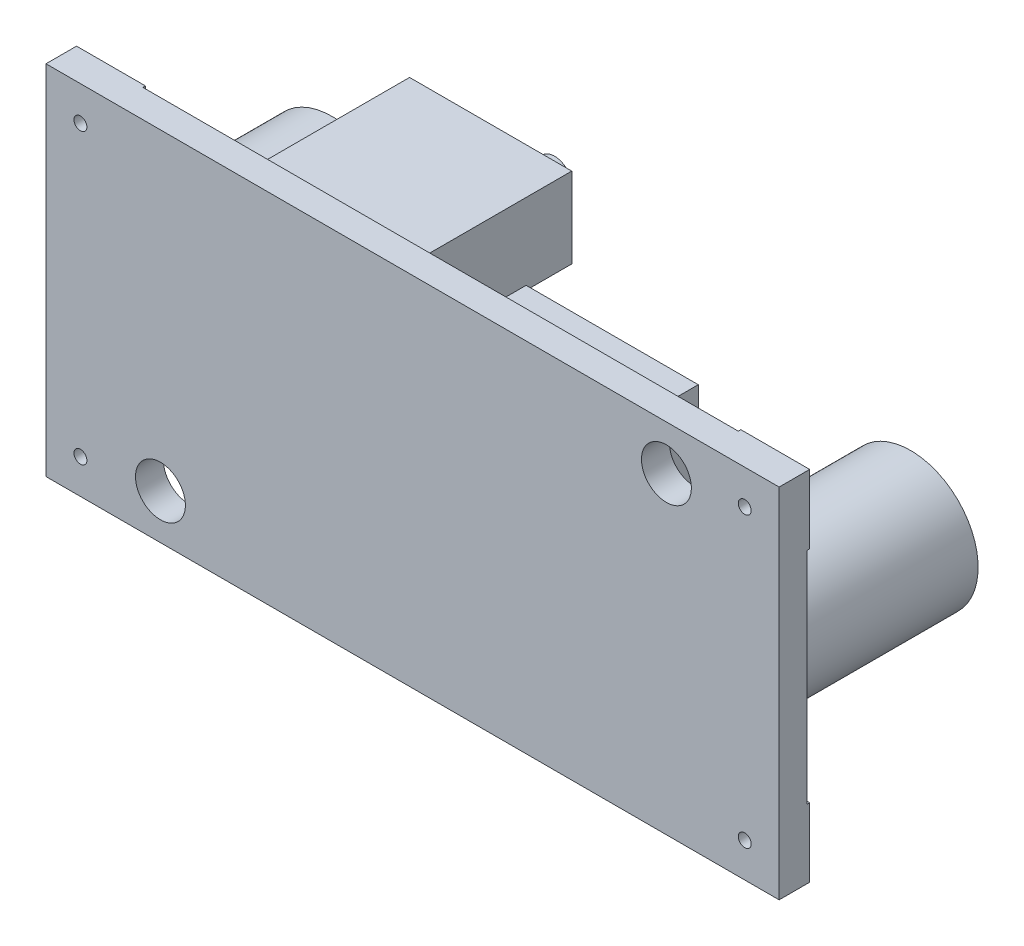
SolidWorks part; units mm, degrees
ref_plane "Front Plane" through (0, 0, 0) normal (0, 0, 1) x (1, 0, 0)
ref_plane "Top Plane" through (0, 0, 0) normal (0, 1, 0) x (1, 0, 0)
ref_plane "Right Plane" through (0, 0, 0) normal (1, 0, 0) x (0, 0, -1)
sketch "Sketch1" plane through (0, 0, 0) normal (0, 0, 1) x (1, 0, 0)
  line L1 (0, 0) -> (43.2816, 0)
  line L2 (0, 0) -> (0, 21.1074)
  line L3 (0, 21.1074) -> (43.2816, 21.1074)
  line L4 (43.2816, 0) -> (43.2816, 21.1074)
  dimension "D1" = 21.1074
  dimension "D2" = 43.2816
extrude "Boss-Extrude1" add sketch "Sketch1" along normal blind 1.651
sketch "Sketch2" plane through (0, 0, 1.651) normal (0, 0, 1) x (1, 0, 0)
  line L0 (5.2832, 2.6416) -> (0, 2.6416)
  line L1 (0, 21.1074) -> (0, 0) construction
  line L2 (6.7564, 1.1684) -> (6.7564, 0)
  line L3 (0, 0) -> (43.2816, 0) construction
  line L4 (36.6268, 19.939) -> (36.6268, 21.1074)
  line L5 (43.2816, 21.1074) -> (0, 21.1074) construction
  line L6 (38.1, 18.4658) -> (43.2816, 18.4658)
  line L7 (43.2816, 0) -> (43.2816, 21.1074) construction
  circle A0 centre (36.6268, 18.4658) radius 1.4732
  circle A1 centre (6.7564, 2.6416) radius 1.4732
  dimension "D1" = 2.9464
  dimension "D2" = 5.1816
  dimension "D3" = 5.2832
  dimension "D4" = 1.1684
  dimension "D5" = 1.1684
extrude "Cut-Extrude1" cut sketch "Sketch2" against normal through all contours A0 | A1
sketch "Sketch3" plane through (0, 0, 0) normal (0, 0, -1) x (-1, 0, 0)
  line L0 (-38.7223, 10.5537) -> (-4.5593, 10.5537) construction
  line L1 (-4.5593, 10.5537) -> (0, 10.5537) construction
  line L2 (0, 21.1074) -> (0, 0) construction
  line L3 (-43.2816, 10.5537) -> (-38.7223, 10.5537) construction
  line L4 (-43.2816, 0) -> (-43.2816, 21.1074) construction
  circle A0 centre (-4.5593, 10.5537) radius 3.9878
  circle A1 centre (-38.7223, 10.5537) radius 3.9878
  dimension "D1" = 7.9756
  dimension "D2" = 7.9756
  dimension "D3" = 34.163
extrude "Boss-Extrude2" add sketch "Sketch3" along normal blind 10.668
sketch "Sketch4" plane through (0, 0, 0) normal (0, 0, -1) x (-1, 0, 0)
  line L0 (0, 0) -> (-43.2816, 0) construction
  line L1 (-21.336, 12.954) -> (-9.652, 12.954)
  line L2 (-21.336, 12.954) -> (-21.336, 1.27)
  line L3 (-21.336, 1.27) -> (-9.652, 1.27)
  line L4 (-9.652, 12.954) -> (-9.652, 1.27)
  line L5 (-21.336, 12.954) -> (-9.652, 1.27) construction
  line L6 (-21.336, 1.27) -> (-9.652, 12.954) construction
  line L7 (0, 21.1074) -> (0, 0) construction
  line L8 (-43.2816, 21.1074) -> (0, 21.1074) construction
  line L9 (-19.7358, 19.8374) -> (-10.16, 19.8374)
  line L10 (-19.7358, 19.8374) -> (-19.7358, 15.0876)
  line L11 (-19.7358, 15.0876) -> (-10.16, 15.0876)
  line L12 (-10.16, 19.8374) -> (-10.16, 15.0876)
  line L13 (-19.7358, 19.8374) -> (-10.16, 15.0876) construction
  line L14 (-19.7358, 15.0876) -> (-10.16, 19.8374) construction
  line L15 (-43.2816, 0) -> (-43.2816, 21.1074) construction
  line L16 (-33.1216, 10.1854) -> (-22.9616, 10.1854)
  line L17 (-33.1216, 10.1854) -> (-33.1216, 18.5674)
  line L18 (-33.1216, 18.5674) -> (-22.9616, 18.5674)
  line L19 (-22.9616, 10.1854) -> (-22.9616, 18.5674)
  line L20 (-33.1216, 10.1854) -> (-22.9616, 18.5674) construction
  line L21 (-33.1216, 18.5674) -> (-22.9616, 10.1854) construction
  point P0 (-15.494, 7.112)
  point P9 (-14.9479, 17.4625)
  point P16 (-28.0416, 14.3764)
  dimension "D1" = 11.684
  dimension "D2" = 11.684
  dimension "D3" = 1.27
  dimension "D4" = 9.652
  dimension "D5" = 9.5758
  dimension "D6" = 4.7498
  dimension "D7" = 10.16
  dimension "D8" = 1.27
  dimension "D9" = 10.16
  dimension "D10" = 8.382
  dimension "D11" = 2.54
  dimension "D12" = 10.16
extrude "Boss-Extrude3" add sketch "Sketch4" along normal blind 3.7338 contours L16 L19 L18 L17
extrude "Boss-Extrude4" add sketch "Sketch4<3>" along normal blind 7.62 contours L1 L4 L3 L2
sketch "Sketch4<3>" plane through (0, 0, 0) normal (0, 0, -1) x (-1, 0, 0) same geometry as "Sketch4"
extrude "Boss-Extrude5" add sketch "Sketch4<4>" along normal blind 9.652 contours L12 L11 L10 L9
sketch "Sketch4<4>" plane through (0, 0, 0) normal (0, 0, -1) x (-1, 0, 0) same geometry as "Sketch4"
sketch "Sketch5" plane through (0, 0, -9.652) normal (0, 0, -1) x (-1, 0, 0)
  line L0 (-19.7358, 19.8374) -> (-10.16, 19.8374) construction
  line L1 (-19.7358, 19.8374) -> (-19.7358, 15.0876) construction
  circle A0 centre (-17.9578, 18.3134) radius 1.016
  dimension "D1" = 2.032
  dimension "D2" = 1.524
  dimension "D3" = 1.778
extrude "Boss-Extrude6" add sketch "Sketch5" along normal blind 0.762
sketch "Sketch6" plane through (0, 0, 0) normal (0, 0, -1) x (-1, 0, 0)
  line L1 (-43.2816, 21.1074) -> (-39.2176, 21.1074)
  line L2 (-43.2816, 21.1074) -> (-43.2816, 17.0434)
  line L3 (-43.2816, 17.0434) -> (-39.2176, 17.0434)
  line L4 (-39.2176, 21.1074) -> (-39.2176, 17.0434)
  line L5 (-43.2816, 0) -> (-39.2176, 0)
  line L6 (-43.2816, 0) -> (-43.2816, 4.064)
  line L7 (-43.2816, 4.064) -> (-39.2176, 4.064)
  line L8 (-39.2176, 0) -> (-39.2176, 4.064)
  line L9 (0, 21.1074) -> (-4.064, 21.1074)
  line L10 (0, 21.1074) -> (0, 17.0434)
  line L11 (0, 17.0434) -> (-4.064, 17.0434)
  line L12 (-4.064, 21.1074) -> (-4.064, 17.0434)
  line L13 (0, 0) -> (-4.064, 0)
  line L14 (0, 0) -> (0, 4.064)
  line L15 (0, 4.064) -> (-4.064, 4.064)
  line L16 (-4.064, 0) -> (-4.064, 4.064)
  dimension "D1" = 4.064
  dimension "D2" = 4.064
extrude "Boss-Extrude7" add sketch "Sketch6" along normal blind 0.1524
sketch "Sketch7" plane through (0, 0, -0.1524) normal (0, 0, -1) x (-1, 0, 0)
  line L0 (-41.2496, 19.0754) -> (-41.2496, 21.1074) construction
  line L1 (-39.2176, 21.1074) -> (-43.2816, 21.1074) construction
  line L2 (-41.2496, 19.0754) -> (-43.2816, 19.0754) construction
  line L3 (-43.2816, 21.1074) -> (-43.2816, 17.0434) construction
  line L4 (-43.2816, 10.5537) -> (0, 10.5537) construction
  line L5 (-43.2816, 4.064) -> (-43.2816, 17.0434) construction
  line L6 (0, 17.0434) -> (0, 4.064) construction
  line L7 (-21.6408, 21.1074) -> (-21.6408, 0) construction
  line L8 (-39.2176, 21.1074) -> (-4.064, 21.1074) construction
  line L9 (-4.064, 0) -> (-39.2176, 0) construction
  circle A0 centre (-41.2496, 19.0754) radius 0.381
  circle A1 centre (-2.032, 19.0754) radius 0.381
  circle A2 centre (-2.032, 2.032) radius 0.381
  circle A3 centre (-41.2496, 2.032) radius 0.381
  dimension "D1" = 0.762
extrude "Cut-Extrude2" cut sketch "Sketch7" against normal through all
